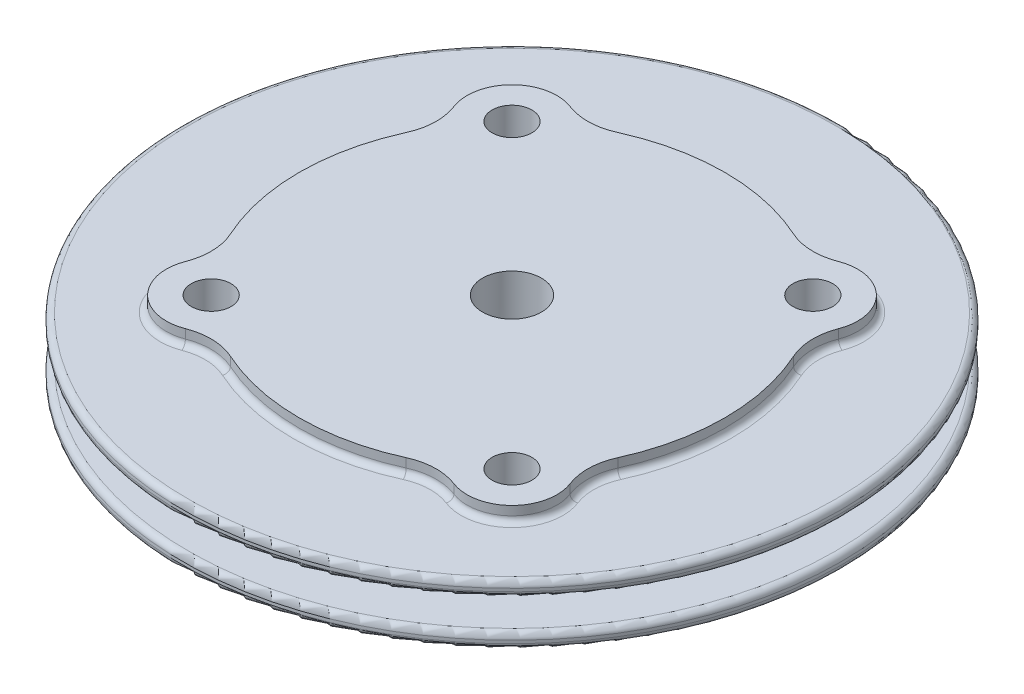
SolidWorks part; units mm, degrees
material "Cast Alloy Steel"
ref_plane "Front" through (0, 0, 0) normal (0, 0, 1) x (1, 0, 0)
ref_plane "Top" through (0, 0, 0) normal (0, 1, 0) x (1, 0, 0)
ref_plane "Right" through (0, 0, 0) normal (1, 0, 0) x (0, 0, -1)
sketch "Sketch1" plane through (0, 0, 0) normal (0, 1, 0) x (1, 0, 0)
  line L1 (-31.8799, -31.8799) -> (31.8799, -31.8799) construction
  line L2 (-31.8799, -31.8799) -> (-31.8799, 31.8799) construction
  line L3 (-31.8799, 31.8799) -> (31.8799, 31.8799) construction
  line L4 (31.8799, -31.8799) -> (31.8799, 31.8799) construction
  line L5 (-31.8799, -31.8799) -> (31.8799, 31.8799) construction
  line L6 (-31.8799, 31.8799) -> (31.8799, -31.8799) construction
  arc A0 (-41.0531, 18.636) -> (-41.0531, -18.636) centre (0, 0) ccw
  arc A1 (-28.4538, 40.7674) -> (-40.7674, 28.4538) centre (-31.8799, 31.8799) ccw
  arc A2 (40.7674, 28.4538) -> (28.4538, 40.7674) centre (31.8799, 31.8799) ccw
  arc A3 (28.4538, -40.7674) -> (40.7674, -28.4538) centre (31.8799, -31.8799) ccw
  arc A4 (18.636, 41.0531) -> (28.4538, 40.7674) centre (23.8856, 52.6173) ccw
  arc A5 (18.636, 41.0531) -> (-18.636, 41.0531) centre (0, 0) ccw
  arc A6 (41.0531, -18.636) -> (41.0531, 18.636) centre (0, 0) ccw
  arc A7 (-18.636, -41.0531) -> (18.636, -41.0531) centre (0, 0) ccw
  arc A8 (-40.7674, -28.4538) -> (-28.4538, -40.7674) centre (-31.8799, -31.8799) ccw
  arc A9 (40.7674, 28.4538) -> (41.0531, 18.636) centre (52.6173, 23.8856) ccw
  arc A10 (40.7674, -28.4538) -> (41.0531, -18.636) centre (52.6173, -23.8856) cw
  arc A11 (18.636, -41.0531) -> (28.4538, -40.7674) centre (23.8856, -52.6173) cw
  arc A12 (-28.4538, -40.7674) -> (-18.636, -41.0531) centre (-23.8856, -52.6173) cw
  arc A13 (-41.0531, -18.636) -> (-40.7674, -28.4538) centre (-52.6173, -23.8856) cw
  arc A14 (-41.0531, 18.636) -> (-40.7674, 28.4538) centre (-52.6173, 23.8856) ccw
  arc A15 (-28.4538, 40.7674) -> (-18.636, 41.0531) centre (-23.8856, 52.6173) ccw
  point P3 (0, 0)
  point P21 (37.866, -24.4709)
  point P26 (-24.4709, -37.866)
  dimension "D1" = 90.17
  dimension "D2" = 19.05
  dimension "D3" = 12.7
extrude "Boss-Extrude1" add sketch "Sketch1" along normal blind 19.05
sketch "Sketch2" plane through (0, 0, 0) normal (0, 0, 1) x (1, 0, 0)
  line L1 (0, 15.875) -> (68.58, 15.875)
  line L2 (0, 15.875) -> (0, 12.7)
  line L3 (0, 12.7) -> (68.58, 12.7)
  line L4 (69.85, 14.605) -> (69.85, 13.97)
  line L5 (0, 6.35) -> (68.58, 6.35)
  line L6 (0, 6.35) -> (0, 3.175)
  line L7 (0, 3.175) -> (68.58, 3.175)
  line L8 (69.85, 5.08) -> (69.85, 4.445)
  line L9 (18.636, 19.05) -> (-18.636, 19.05) construction
  line L10 (0, 0) -> (0, 36.1887) construction
  arc A0 (68.58, 3.175) -> (69.85, 4.445) centre (68.58, 4.445) ccw
  arc A1 (68.58, 6.35) -> (69.85, 5.08) centre (68.58, 5.08) cw
  arc A2 (68.58, 12.7) -> (69.85, 13.97) centre (68.58, 13.97) ccw
  arc A3 (68.58, 15.875) -> (69.85, 14.605) centre (68.58, 14.605) cw
  point P22 (69.85, 12.7)
  point P25 (69.85, 15.875)
  dimension "D5" = 1.27
  dimension "D1" = 3.175
  dimension "D2" = 3.175
  dimension "D3" = 9.525
  dimension "D4" = 139.7
revolve "Revolve1" add sketch "Sketch2" angle 360 about L10
sketch "Sketch3" plane through (0, 0, 0) normal (0, 0, 1) x (1, 0, 0)
  line L0 (28.4538, 0) -> (41.4049, 0) construction
  line L1 (0, 1.27) -> (33.1998, 1.27) construction
  line L2 (0, 0) -> (0, 9.476) construction
  line L3 (0, 1.27) -> (0, 0)
  line L4 (0, 0) -> (38.1, 0)
  arc A0 (38.1, 0) -> (0, 1.27) centre (0, -570.865) ccw
  dimension "D1" = 1.27
  dimension "D2" = 76.2
revolve "Cut-Revolve1" cut sketch "Sketch3" angle 360 about L2
hole_wizard "M14x1.5 Tapped Hole1" positions "Sketch5" profile "Sketch4" tap size "M14x1.5" standard "ANSI Metric" end condition through all
sketch "Sketch5" plane through (0, 19.05, 0) normal (0, 1, 0) x (1, 0, 0)
  point P0 (0, 0)
sketch "Sketch4" plane through (0, 19.05, 0) normal (1, 0, 0) x (0, 0, 1)
  line L0 (0, 0) -> (0, 19.05)
  line L1 (0, 19.05) -> (6.25, 19.05)
  line L2 (6.25, 19.05) -> (6.25, 0)
  line L5 (6.25, 0) -> (0, 0)
  line L11 (0, -6.35) -> (0, 107.95) construction
  dimension "Thru Tap Drill Dia." = 12.5
  dimension "Thru Tap Drill Depth" = 19.05
cosmetic thread "Hole Thread1" parameters "D2"=14
sketch "Sketch6" plane through (0, 19.05, 0) normal (0, 1, 0) x (1, 0, 0)
  circle A0 centre (-31.8799, 31.8799) radius 4.2164
  circle A1 centre (31.8799, 31.8799) radius 4.2164
  circle A2 centre (31.8799, -31.8799) radius 4.2164
  circle A3 centre (-31.8799, -31.8799) radius 4.2164
  dimension "D1" = 8.4328
extrude "Cut-Extrude1" cut sketch "Sketch6" against normal through all
fillet "Fillet1" radius 8.89 1 edges at (0, 1.2359, -6.25)
fillet "Fillet2" radius 1.27 64 edges at (23.5161, 12.7, -39.9227) (38.6151, 12.7, -38.6151) (39.9227, 12.7, -23.5161) (45.085, 12.7, 0) (39.9227, 12.7, 23.5161) (38.6151, 12.7, 38.6151) (23.5161, 12.7, 39.9227) (0, 12.7, 45.085) (-23.5161, 12.7, 39.9227) (-38.6151, 12.7, 38.6151) (-39.9227, 12.7, 23.5161) (-45.085, 12.7, 0) (-39.9227, 12.7, -23.5161) (-38.6151, 12.7, -38.6151) (-23.5161, 12.7, -39.9227) (0, 12.7, -45.085) (-23.5161, 15.875, -39.9227) (-38.6151, 15.875, -38.6151) (-39.9227, 15.875, -23.5161) (-45.085, 15.875, 0) (-39.9227, 15.875, 23.5161) (-38.6151, 15.875, 38.6151) (-23.5161, 15.875, 39.9227) (0, 15.875, 45.085) (23.5161, 15.875, 39.9227) (38.6151, 15.875, 38.6151) (39.9227, 15.875, 23.5161) (45.085, 15.875, 0) (39.9227, 15.875, -23.5161) (38.6151, 15.875, -38.6151) (23.5161, 15.875, -39.9227) (0, 15.875, -45.085) (23.5161, 3.175, -39.9227) (38.6151, 3.175, -38.6151) (39.9227, 3.175, -23.5161) (45.085, 3.175, 0) (39.9227, 3.175, 23.5161) (38.6151, 3.175, 38.6151) (23.5161, 3.175, 39.9227) (0, 3.175, 45.085) (-23.5161, 3.175, 39.9227) (-38.6151, 3.175, 38.6151) (-39.9227, 3.175, 23.5161) (-45.085, 3.175, 0) (-39.9227, 3.175, -23.5161) (-38.6151, 3.175, -38.6151) (-23.5161, 3.175, -39.9227) (0, 3.175, -45.085) (-23.5161, 6.35, -39.9227) (-38.6151, 6.35, -38.6151) (-39.9227, 6.35, -23.5161) (-45.085, 6.35, 0) (-39.9227, 6.35, 23.5161) (-38.6151, 6.35, 38.6151) (-23.5161, 6.35, 39.9227) (0, 6.35, 45.085) (23.5161, 6.35, 39.9227) (38.6151, 6.35, 38.6151) (39.9227, 6.35, 23.5161) (45.085, 6.35, 0) (39.9227, 6.35, -23.5161) (38.6151, 6.35, -38.6151) (23.5161, 6.35, -39.9227) (0, 6.35, -45.085)
